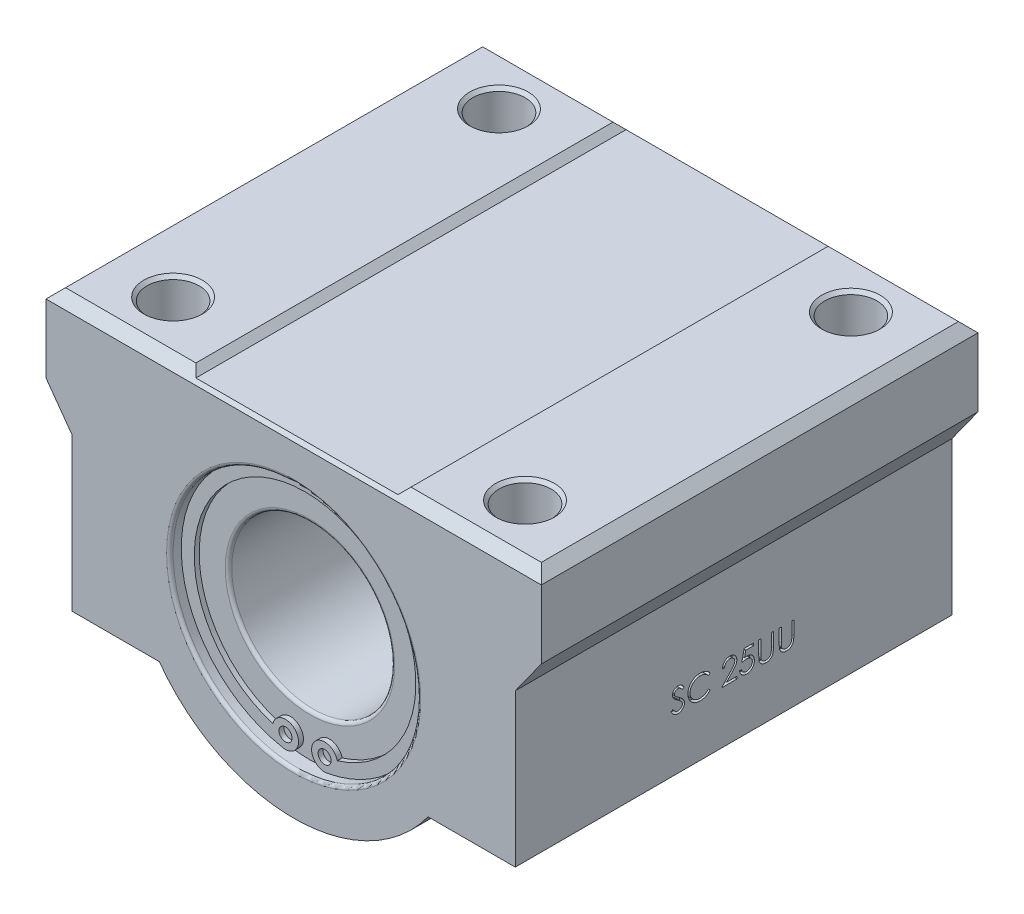
SolidWorks part; units mm, degrees
ref_plane "Front Plane" through (0, 0, 0) normal (0, 0, 1) x (1, 0, 0)
ref_plane "Top Plane" through (0, 0, 0) normal (0, 1, 0) x (1, 0, 0)
ref_plane "Right Plane" through (0, 0, 0) normal (1, 0, 0) x (0, 0, -1)
sketch "Sketch1" plane through (0, 0, 0) normal (0, 0, 1) x (1, 0, 0)
  line L0 (38, 14) -> (34, 8.4344)
  line L1 (0, 26) -> (0, -25.5) construction
  line L2 (-20.6216, -15) -> (-34, -15)
  line L3 (38, 26) -> (-38, 26)
  line L4 (-34, -15) -> (-34, 8.4344)
  line L5 (-38, 26) -> (-38, 14)
  line L6 (-38, 14) -> (-34, 8.4344)
  line L7 (38, 26) -> (38, 14)
  line L8 (34, -15) -> (34, 8.4344)
  line L9 (20.6216, -15) -> (34, -15)
  circle A0 centre (0, 0) radius 12.5
  arc A1 (-20.6216, -15) -> (20.6216, -15) centre (0, 0) ccw
  dimension "D1" = 25
  dimension "D2" = 38
  dimension "D3" = 26
  dimension "D5" = 34
  dimension "D6" = 41
  dimension "D7" = 12
extrude "Boss-Extrude1" add sketch "Sketch1" along normal blind 67
sketch "Sketch2" plane through (0, 26, 0) normal (0, 1, 0) x (1, 0, 0)
  line L0 (-38, -67) -> (-38, 0) construction
  line L1 (38, -67) -> (-38, -67) construction
  circle A0 centre (-27, -58.5) radius 4
  circle A1 centre (27, -58.5) radius 4
  circle A2 centre (27, -8.5) radius 4
  circle A3 centre (-27, -8.5) radius 4
  dimension "D1" = 8
  dimension "D2" = 11
  dimension "D6" = 54
  dimension "D7" = 50
  dimension "D3" = 8.5
  dimension "D4" = 2
  dimension "D5" = 2
extrude "Cut-Extrude1" cut sketch "Sketch2" against normal blind 18
sketch "Sketch3" plane through (0, 26, 0) normal (0, 1, 0) x (1, 0, 0)
  circle A0 centre (-27, -58.5) radius 3
  circle A1 centre (27, -58.5) radius 3
  circle A2 centre (27, -8.5) radius 3
  circle A3 centre (-27, -8.5) radius 3
  dimension "D1" = 6
  dimension "D2" = 2
  dimension "D3" = 2
extrude "Cut-Extrude2" cut sketch "Sketch3" against normal through all
sketch "Sketch4" plane through (0, 26, 0) normal (0, 1, 0) x (1, 0, 0)
  line L0 (38, -67) -> (-38, -67) construction
  line L1 (15, 0) -> (-15, 0)
  line L3 (15, -67) -> (-15, -67)
  line L4 (-15, 0) -> (-15, -67)
  line L5 (0, 0) -> (0, 12.592) construction
  line L6 (15, 0) -> (15, -67)
  dimension "D1" = 15
  dimension "D2" = 30
  dimension "D3" = 67
extrude "Cut-Extrude3" cut sketch "Sketch4" against normal blind 1
chamfer "Chamfer2" distance 1.5 angle 45 2 edges at (-38, 26, 33.5) (38, 26, 33.5)
chamfer "Chamfer3" distance 1.5 angle 45 2 edges at (-25.75, 26, 0) (-25.75, 26, 67)
chamfer "Chamfer4" distance 1.5 angle 45 2 edges at (15, 26, 33.5) (-15, 26, 33.5)
sketch "Sketch5" plane through (0, 0, 67) normal (0, 0, 1) x (1, 0, 0)
  circle A0 centre (0, 0) radius 19
  dimension "D1" = 38
extrude "Cut-Extrude4" cut sketch "Sketch5" against normal blind 2.5
sketch "Sketch6" plane through (0, 0, 0) normal (0, 0, -1) x (-1, 0, 0)
  circle A0 centre (0, 0) radius 19 construction
  circle A1 centre (0, 0) radius 19
extrude "Cut-Extrude5" cut sketch "Sketch6" against normal blind 2.5
fillet "Fillet2" radius 0.5 1 edges at (19, 0, 67)
fillet "Fillet3" radius 0.5 1 edges at (-19, 0, 0)
fillet "Fillet4" radius 0.5 1 edges at (-12.5, 0, 2.5)
fillet "Fillet5" radius 0.5 1 edges at (12.5, 0, 64.5)
sketch "Sketch7" plane through (34, 0, 0) normal (1, 0, 0) x (0, 0, -1)
  line L0 (-67, -7.5) -> (0, -7.5) construction
  line L1 (-67, -15) -> (-67, 8.4344) construction
  line L2 (0, -15) -> (0, 8.4344) construction
  line L3 (-67, -15) -> (0, -15) construction
  text T0 "THK  SC 25UU"
  dimension "D1" = 7.5
extrude "Cut-Extrude6" cut sketch "Sketch7" against normal blind 0.5
chamfer "Chamfer5" distance 0.5 angle 45 4 edges at (-31, 26, 58.5) (23, 26, 58.5) (-31, 26, 8.5) (23, 26, 8.5)
sketch "Sketch9" plane through (0, 0, 2.5) normal (0, 0, -1) x (-1, 0, 0)
  line L0 (0, 0) -> (0, -19) construction
  circle A0 centre (0, 0) radius 19 construction
  arc A1 (3.3529, -18.7018) -> (-3.3529, -18.7018) centre (0, 0) ccw
  arc A3 (-3.3529, -18.7018) -> (-4.9444, -16.2651) centre (-3, -16.7332) ccw
  circle A4 centre (-3, -16.7332) radius 1
  circle A5 centre (3, -16.7332) radius 1
  arc A6 (3.3529, -18.7018) -> (4.9444, -16.2651) centre (3, -16.7332) cw
  arc A9 (4.9444, -16.2651) -> (-4.9444, -16.2651) centre (0, 0) ccw
  dimension "D2" = 4
  dimension "D4" = 2
  dimension "D3" = 3
extrude "Boss-Extrude2" add sketch "Sketch9" along normal blind 0.75
sketch "Sketch10" plane through (0, 0, 64.5) normal (0, 0, 1) x (1, 0, 0)
  circle A0 centre (-3, -16.7332) radius 1 construction
  circle A1 centre (-3, -16.7332) radius 1
  circle A2 centre (3, -16.7332) radius 1 construction
  circle A3 centre (3, -16.7332) radius 1
  arc A4 (-3.3529, -18.7018) -> (-4.9444, -16.2651) centre (-3, -16.7332) ccw
  arc A5 (3.3529, -18.7018) -> (-3.3529, -18.7018) centre (0, 0) ccw
  arc A6 (4.9444, -16.2651) -> (3.3529, -18.7018) centre (3, -16.7332) ccw
  arc A7 (4.9444, -16.2651) -> (-4.9444, -16.2651) centre (0, 0) ccw
  arc A8 (-3.3529, -18.7018) -> (-4.9444, -16.2651) centre (-3, -16.7332) ccw
  arc A9 (3.3529, -18.7018) -> (-3.3529, -18.7018) centre (0, 0) ccw
  arc A10 (4.9444, -16.2651) -> (3.3529, -18.7018) centre (3, -16.7332) ccw
  arc A11 (4.9444, -16.2651) -> (-4.9444, -16.2651) centre (0, 0) ccw
  dimension "D1" = 0
extrude "Boss-Extrude3" add sketch "Sketch10" along normal blind 0.75
sketch "Sketch11" plane through (34, 0, 0) normal (1, 0, 0) x (0, 0, -1)
  line L1 (-55.4163, 1.3949) -> (-14.9638, 1.3949)
  line L2 (-55.4163, 1.3949) -> (-55.4163, -11.9075)
  line L3 (-55.4163, -11.9075) -> (-14.9638, -11.9075)
  line L4 (-14.9638, 1.3949) -> (-14.9638, -11.9075)
extrude "Boss-Extrude4" add sketch "Sketch11" against normal blind 0.75
sketch "Sketch12" plane through (34, 0, 0) normal (1, 0, 0) x (0, 0, -1)
  line L0 (-67, -7) -> (0, -7) construction
  line L1 (-67, -15) -> (-67, 8.4344) construction
  line L2 (0, -15) -> (0, 8.4344) construction
  line L3 (-67, -15) -> (0, -15) construction
  text T0 "SC 25UU"
  dimension "D1" = 8
extrude "Cut-Extrude7" cut sketch "Sketch12" against normal blind 0.75
scale "Scale1" bodies to scale 111 scale about centroid uniform scaling yes scale factor 0.32
